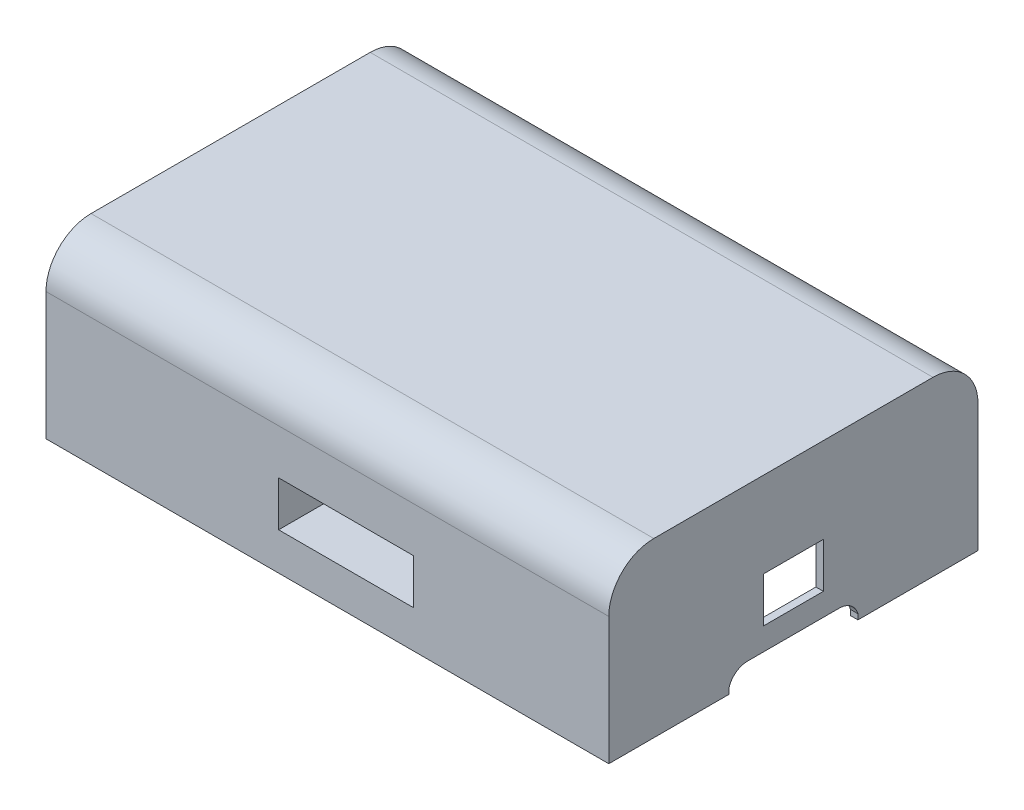
SolidWorks part; units mm, degrees
ref_plane "Front Plane" through (0, 0, 0) normal (0, 0, 1) x (1, 0, 0)
ref_plane "Top Plane" through (0, 0, 0) normal (0, 1, 0) x (1, 0, 0)
ref_plane "Right Plane" through (0, 0, 0) normal (1, 0, 0) x (0, 0, -1)
sketch "Sketch1" plane through (0, 0, 0) normal (0, 1, 0) x (1, 0, 0)
  line L1 (-17, 9.3) -> (17, 9.3)
  line L2 (-17, 9.3) -> (-17, -9.3)
  line L3 (-17, -9.3) -> (17, -9.3)
  line L4 (17, 9.3) -> (17, -9.3)
  line L5 (-17, 9.3) -> (17, -9.3) construction
  line L6 (-17, -9.3) -> (17, 9.3) construction
  line L7 (-20, 12.3) -> (20, 12.3)
  line L8 (-20, 12.3) -> (-20, -12.3)
  line L9 (-20, -12.3) -> (20, -12.3)
  line L10 (20, 12.3) -> (20, -12.3)
  line L11 (-20, 12.3) -> (20, -12.3) construction
  line L12 (-20, -12.3) -> (20, 12.3) construction
  point P0 (0, 0)
  point P6 (0, 0)
  dimension "D1" = 34
  dimension "D2" = 18.6
  dimension "D3" = 3
  dimension "D4" = 3
extrude "Boss-Extrude1" add sketch "Sketch1" along normal blind 14
ref_plane "Plane1" through (0, 5.5, 0) normal (0, -1, 0) x (-1, 0, 0)
sketch "Sketch3" plane through (20, 0, 0) normal (1, 0, 0) x (0, 0, -1)
  line L0 (-13.53, 5.5) -> (13.53, 5.5) construction
  line L1 (-3.05, 5.5) -> (3.05, 5.5) construction
  line L2 (-3.05, 6.8) -> (3.05, 6.8)
  line L3 (-3.05, 4.2) -> (3.05, 4.2)
  line L5 (-4.3, 6.8) -> (4.3, 6.8)
  line L6 (-4.3, 6.8) -> (-4.3, 4.2)
  line L7 (-4.3, 4.2) -> (4.3, 4.2)
  line L8 (4.3, 6.8) -> (4.3, 4.2)
  line L9 (-4.3, 6.8) -> (4.3, 4.2) construction
  line L10 (-4.3, 4.2) -> (4.3, 6.8) construction
  arc A0 (-3.05, 6.8) -> (-3.05, 4.2) centre (-3.05, 5.5) ccw
  arc A1 (3.05, 4.2) -> (3.05, 6.8) centre (3.05, 5.5) ccw
  point P4 (0, 5.5)
  point P9 (0, 5.5)
  dimension "D4" = 1.25
  dimension "D1" = 8.6
  dimension "D2" = 2.6
  dimension "D3" = 0
  dimension "D5" = 0
extrude "Cut-Extrude1" cut sketch "Sketch3" against normal blind 10 contours A1 L2 A0 L3 region at (20, 5.5, 0)
split "Split1" trim tools "Plane1" bodies to split 102 resulting bodies 103 104
sketch "Sketch5" plane through (20, 0, 0) normal (1, 0, 0) x (0, 0, -1)
  line L0 (-3.05, 6.8) -> (3.05, 6.8) construction
  line L1 (-2, 11.3) -> (2, 11.3)
  line L2 (-2, 11.3) -> (-2, 8.3)
  line L3 (-2, 8.3) -> (2, 8.3)
  line L4 (2, 11.3) -> (2, 8.3)
  line L5 (-2, 11.3) -> (2, 8.3) construction
  line L6 (-2, 8.3) -> (2, 11.3) construction
  point P0 (0, 9.8)
  dimension "D1" = 3
  dimension "D2" = 4
  dimension "D3" = 0
  dimension "D4" = 1.5
extrude "Cut-Extrude2" cut sketch "Sketch5" against normal blind 10
sketch "Sketch6" plane through (20, 0, 0) normal (1, 0, 0) x (0, 0, -1)
  line L0 (-12.3, 14) -> (12.3, 14) construction
  line L1 (-9.3, 17) -> (9.3, 17)
  line L2 (-12.3, 14) -> (12.3, 14)
  arc A0 (-12.3, 14) -> (-9.3, 17) centre (-9.3, 14) cw
  arc A1 (12.3, 14) -> (9.3, 17) centre (9.3, 14) ccw
  dimension "D3" = 3
  dimension "D1" = 3
  dimension "D2" = 3
extrude "Boss-Extrude2" add sketch "Sketch6" against normal blind 40 contours L1 A1 L2 A0
sketch "Sketch7" plane through (-20, 0, 0) normal (-1, 0, 0) x (0, 0, 1)
  line L0 (-12.3, 0) -> (12.3, 0) construction
  line L1 (12.3, 5.5) -> (12.3, 0) construction
  line L2 (-12.3, 5.5) -> (-12.3, 0) construction
  line L3 (-9.3, -3) -> (9.3, -3)
  line L4 (12.3, 0) -> (-12.3, 0)
  arc A0 (-12.3, 0) -> (-9.3, -3) centre (-9.3, 0) ccw
  arc A1 (12.3, 0) -> (9.3, -3) centre (9.3, 0) cw
  dimension "D1" = 3
  dimension "D2" = 3
  dimension "D3" = 0
  dimension "D4" = 0
extrude "Boss-Extrude3" add sketch "Sketch7" against normal blind 40
sketch "Sketch8" plane through (0, 0, 12.3) normal (0, 0, 1) x (1, 0, 0)
  line L1 (4, 0.5) -> (-4, 0.5)
  line L2 (4, 0.5) -> (4, 12.5)
  line L3 (4, 12.5) -> (-4, 12.5)
  line L4 (-4, 0.5) -> (-4, 12.5)
  line L5 (4, 0.5) -> (-4, 12.5) construction
  line L6 (4, 12.5) -> (-4, 0.5) construction
  line L7 (20, 5.5) -> (-20, 5.5) construction
  point P0 (0, 6.5)
  dimension "D1" = 8
  dimension "D2" = 12
  dimension "D3" = 5
  dimension "D4" = 0
extrude "Boss-Extrude4" add sketch "Sketch8" along normal blind 2
fillet "Fillet4" radius 21 1 edges at (0, 0.5, 14.3)
sketch "Sketch10" plane through (0, 0, 12.3) normal (0, 0, -1) x (-1, 0, 0)
  line L0 (4, 12.5) -> (4, 5.5) construction
  line L1 (-4, 10.5) -> (4, 10.5)
  line L2 (-4, 10.5) -> (-4, 8.5)
  line L3 (-4, 8.5) -> (4, 8.5)
  line L4 (4, 10.5) -> (4, 8.5)
  line L5 (-4, 10.5) -> (4, 8.5) construction
  line L6 (-4, 8.5) -> (4, 10.5) construction
  line L7 (-4, 5.5) -> (-4, 12.5) construction
  line L8 (-4, 12.5) -> (4, 12.5) construction
  point P0 (0, 9.5)
  dimension "D1" = 2
  dimension "D2" = 2
  dimension "D3" = 0
extrude "Boss-Extrude6" add sketch "Sketch10" along normal blind 1
sketch "Sketch13" plane through (0, 0, -12.3) normal (0, 0, -1) x (-1, 0, 0)
  line L0 (20, 5.5) -> (-20, 5.5) construction
  line L1 (-13, 5.5) -> (-11, 5.5)
  line L2 (-13, 5.5) -> (-13, 11.5)
  line L3 (-13, 11.5) -> (-11, 11.5)
  line L4 (-11, 5.5) -> (-11, 11.5)
  line L5 (0, 0) -> (0, -9.2638) construction
  line L6 (11, 5.5) -> (11, 11.5)
  line L7 (13, 11.5) -> (11, 11.5)
  line L8 (13, 5.5) -> (13, 11.5)
  line L9 (13, 5.5) -> (11, 5.5)
  line L10 (-20, 5.5) -> (-20, 0) construction
  dimension "D1" = 6
  dimension "D2" = 2
  dimension "D3" = 7
extrude "Boss-Extrude7" add sketch "Sketch13" against normal blind 1.5
sketch "Sketch14" plane through (0, 0, -10.8) normal (0, 0, 1) x (1, 0, 0)
  line L0 (-11, 11.5) -> (-11, 5.5) construction
  line L1 (-13, 11.5) -> (-11, 11.5)
  line L2 (-13, 11.5) -> (-13, 8.5)
  line L3 (-13, 8.5) -> (-11, 8.5)
  line L4 (-11, 11.5) -> (-11, 8.5)
  line L5 (13, 11.5) -> (13, 5.5) construction
  line L6 (11, 11.5) -> (13, 11.5)
  line L7 (11, 11.5) -> (11, 8.5)
  line L8 (11, 8.5) -> (13, 8.5)
  line L9 (13, 11.5) -> (13, 8.5)
  dimension "D1" = 3
  dimension "D2" = 3
extrude "Boss-Extrude9" add sketch "Sketch14" along normal blind 1 contours L8 L9 L6 L7
extrude "Boss-Extrude10" add sketch "Sketch14<4>" along normal blind 1
sketch "Sketch14<4>" plane through (0, 0, -10.8) normal (0, 0, 1) x (1, 0, 0) same geometry as "Sketch14"
sketch "Sketch15" plane through (13, 0, 0) normal (1, 0, 0) x (0, 0, -1)
  line L0 (9.8, 8.5) -> (11.05, 11.5)
  line L1 (9.8, 11.5) -> (12.3, 11.5) construction
  line L2 (11.05, 11.5) -> (9.8, 11.5)
  line L3 (9.8, 11.5) -> (9.8, 8.5)
extrude "Cut-Extrude5" cut sketch "Sketch15" against normal blind 28
sketch "Sketch16" plane through (4, 0, 0) normal (1, 0, 0) x (0, 0, -1)
  line L0 (-14.3, 12.5) -> (-12.3, 10.5)
  line L1 (-12.3, 10.5) -> (-12.3, 12.5)
  line L2 (-12.3, 12.5) -> (-14.3, 12.5)
extrude "Cut-Extrude6" cut sketch "Sketch16" against normal blind 28
fillet "Fillet8" radius 0.5 1 edges at (0, 12.5, 14.3)
sketch "Sketch21" plane through (4, 0, 0) normal (1, 0, 0) x (0, 0, -1)
  line L0 (-12.3, 10.5) -> (-11.3, 8.5)
  line L1 (-11.3, 8.5) -> (-11.3, 10.5)
  line L2 (-11.3, 10.5) -> (-12.3, 10.5)
extrude "Cut-Extrude9" cut sketch "Sketch21" against normal blind 26
combine bodies "Combine1" operation type subtract main body 106 bodies to subtract 125
sketch "Sketch22" plane through (0, 0, 12.3) normal (0, 0, 1) x (1, 0, 0)
  line L1 (-4, 10.5) -> (4, 10.5)
  line L2 (-4, 10.5) -> (-4, 8.5)
  line L3 (-4, 8.5) -> (4, 8.5)
  line L4 (4, 10.5) -> (4, 8.5)
  line L5 (-4.5, 11) -> (4.5, 11)
  line L6 (-4.5, 11) -> (-4.5, 8)
  line L7 (-4.5, 8) -> (4.5, 8)
  line L8 (4.5, 11) -> (4.5, 8)
  dimension "D1" = 0.5
  dimension "D2" = 0.5
  dimension "D3" = 0.5
  dimension "D4" = 0.5
extrude "Cut-Extrude10" cut sketch "Sketch22" against normal blind 5
sketch "Sketch24" plane through (0, 0, 12.3) normal (0, 0, 1) x (1, 0, 0)
  line L1 (-4, 10.5) -> (4, 10.5)
  line L2 (-4, 10.5) -> (-4, 8.5)
  line L3 (-4, 8.5) -> (4, 8.5)
  line L4 (4, 10.5) -> (4, 8.5)
extrude "Cut-Extrude11" cut sketch "Sketch24" against normal blind 5
sketch "Sketch25" plane through (0, 0, -12.3) normal (0, 0, -1) x (-1, 0, 0)
  line L0 (11, 5.5) -> (-11, 5.5) construction
  line L1 (-13.5, 12) -> (-10.5, 12)
  line L2 (-13.5, 12) -> (-13.5, 5.5)
  line L3 (-13.5, 5.5) -> (-10.5, 5.5)
  line L4 (-10.5, 12) -> (-10.5, 5.5)
  line L5 (20, 5.5) -> (13, 5.5) construction
  line L6 (10.5, 12) -> (13.5, 12)
  line L7 (10.5, 12) -> (10.5, 5.5)
  line L8 (10.5, 5.5) -> (13.5, 5.5)
  line L9 (13.5, 12) -> (13.5, 5.5)
  line L10 (-13, 11.5) -> (-13, 5.5) construction
  line L11 (-11, 11.5) -> (-11, 8.5) construction
  line L12 (-11, 11.5) -> (-13, 11.5) construction
  line L13 (13, 11.5) -> (11, 11.5) construction
  line L14 (11, 8.5) -> (11, 11.5) construction
  line L15 (13, 11.5) -> (13, 8.5) construction
  dimension "D1" = 0.5
  dimension "D2" = 0.5
  dimension "D3" = 0.5
  dimension "D4" = 0.5
  dimension "D5" = 0.5
  dimension "D6" = 0.5
extrude "Cut-Extrude12" cut sketch "Sketch25" against normal blind 5
sketch "Sketch26" plane through (13.5, 0, 0) normal (-1, 0, 0) x (0, 0, 1)
  line L1 (-9.3, 5.5) -> (-10.7, 5.5)
  line L2 (-9.3, 5.5) -> (-9.3, 8.3)
  line L3 (-9.3, 8.3) -> (-10.7, 8.3)
  line L4 (-10.7, 5.5) -> (-10.7, 8.3)
  dimension "D1" = 1.4
  dimension "D2" = 2.8
extrude "Boss-Extrude12" add sketch "Sketch26" along normal blind 28
sketch "Sketch20" plane through (0, 17, 0) normal (0, 1, 0) x (1, 0, 0)
  line L0 (-20, -12.3) -> (20, -12.3) construction
  line L1 (20, 12.3) -> (17.5, 12.3)
  line L2 (20, 12.3) -> (20, -12.3)
  line L3 (20, -12.3) -> (17.5, -12.3)
  line L4 (17.5, 12.3) -> (17.5, -12.3)
  dimension "D1" = 2.5
extrude "Cut-Extrude8" cut sketch "Sketch20" against normal blind 26
